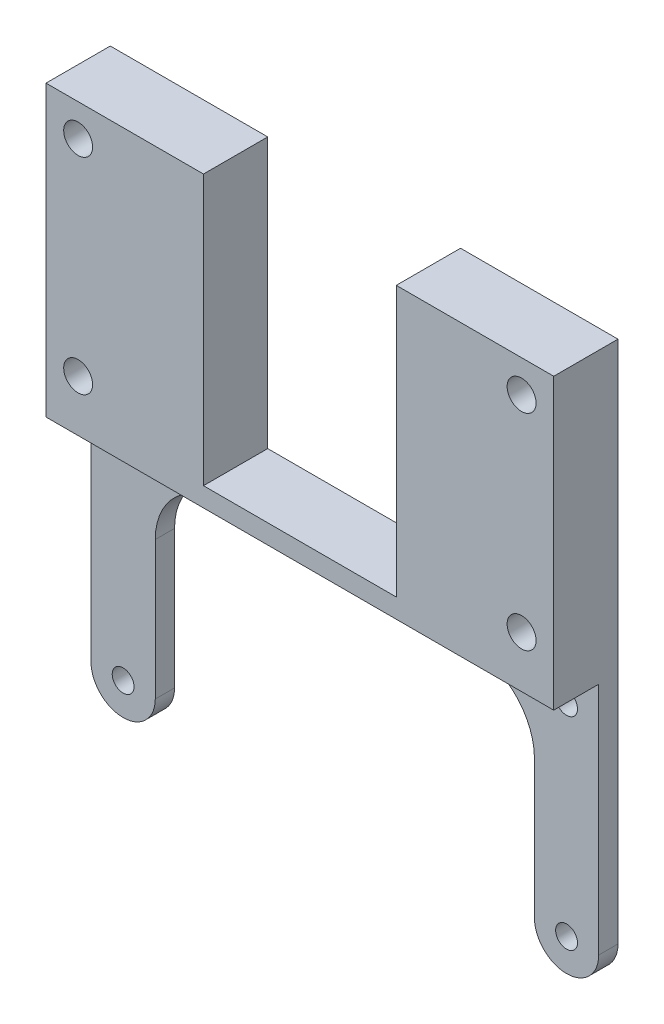
SolidWorks part; units mm, degrees
ref_plane "Front Plane" through (0, 0, 0) normal (0, 0, 1) x (1, 0, 0)
ref_plane "Top Plane" through (0, 0, 0) normal (0, 1, 0) x (1, 0, 0)
ref_plane "Right Plane" through (0, 0, 0) normal (1, 0, 0) x (0, 0, -1)
sketch "Sketch1" plane through (0, 0, 0) normal (0, 0, 1) x (1, 0, 0)
  line L0 (28.0246, -31.0442) -> (28.0246, 7.8468)
  line L1 (-40.9754, 12.8468) -> (38.0246, 12.8468)
  line L2 (-40.9754, 12.8468) -> (-40.9754, -28.6532)
  line L3 (-40.9754, -28.6532) -> (38.0246, -28.6532)
  line L4 (38.0246, 12.8468) -> (38.0246, -28.6532)
  line L5 (28.0246, -31.0442) -> (-30.9754, -31.0442)
  line L6 (28.0246, 7.8468) -> (-30.9754, 7.8468)
  line L7 (-30.9754, -31.0442) -> (-30.9754, 7.8468)
  line L8 (28.0246, -31.0442) -> (-30.9754, 7.8468) construction
  line L9 (28.0246, 7.8468) -> (-30.9754, -31.0442) construction
  point P5 (-1.4754, -11.5987)
  dimension "D1" = 79
  dimension "D2" = 41.5
  dimension "D3" = 5
  dimension "D4" = 10
  dimension "D5" = 10
extrude "Boss-Extrude1" add sketch "Sketch1" along normal blind 3 contours L3 L7 L6 L0 L4 L1 L2 region at (28.9169, -10.4032, 0)
fillet "Fillet1" radius 10 2 edges at (28.0246, 7.8468, 1.5) (-30.9754, 7.8468, 1.5)
fillet "Fillet2" radius 5 4 edges at (-30.9754, -28.6532, 1.5) (-40.9754, -28.6532, 1.5) (28.0246, -28.6532, 1.5) (38.0246, -28.6532, 1.5)
sketch "Sketch2" plane through (0, 0, 0) normal (0, 0, -1) x (-1, 0, 0)
  line L0 (40.9754, 12.8468) -> (40.9754, -23.6532) construction
  line L2 (40.9754, 12.8468) -> (-38.0246, 12.8468) construction
  line L3 (-38.0246, 12.8468) -> (-38.0246, -23.6532) construction
  point P0 (-33.0246, 7.8468)
  point P1 (35.9754, -23.6532)
  point P4 (-33.0246, -23.6532)
  point P11 (35.9754, 7.8468)
  dimension "D1" = 5
  dimension "D2" = 5
  dimension "D3" = 5
  dimension "D4" = 5
  dimension "D5" = 5
  dimension "D6" = 5
  dimension "D7" = 5
  dimension "D8" = 5
hole_wizard "M3 Clearance Hole1" positions "Sketch3" profile "Sketch4" hole size "M3" standard "ANSI Metric" end condition through all
sketch "Sketch3" plane through (0, 0, 0) normal (0, 0, -1) x (-1, 0, 0)
  point P0 (-33.0246, 7.8468)
  point P6 (35.9754, -23.6532)
  point P9 (35.9754, 7.8468)
  point P17 (-33.0246, -23.6532)
sketch "Sketch4" plane through (33.0246, 7.8468, 0) normal (1, 0, 0) x (0, 1, 0)
  line L0 (0, 0) -> (0, 3)
  line L1 (0, 3) -> (1.7, 3)
  line L2 (1.7, 3) -> (1.7, 0)
  line L5 (1.7, 0) -> (0, 0)
  line L11 (0, -6.35) -> (0, 107.95) construction
  dimension "Thru Hole Dia." = 3.4
  dimension "Thru Hole Depth" = 3
sketch "Sketch5" plane through (0, 0, 0) normal (0, 0, -1) x (-1, 0, 0)
  line L0 (40.9754, 12.8468) -> (40.9754, -23.6532) construction
  line L1 (-38.0246, 12.8468) -> (40.9754, 12.8468)
  line L2 (-38.0246, 12.8468) -> (-38.0246, 57.8468)
  line L3 (-38.0246, 57.8468) -> (40.9754, 57.8468)
  line L4 (40.9754, 12.8468) -> (40.9754, 57.8468)
  line L6 (16.4754, 15.8468) -> (-13.5246, 15.8468)
  line L7 (16.4754, 15.8468) -> (16.4754, 57.8468)
  line L8 (16.4754, 57.8468) -> (-13.5246, 57.8468)
  line L9 (-13.5246, 15.8468) -> (-13.5246, 57.8468)
  line L10 (16.4754, 15.8468) -> (-13.5246, 57.8468) construction
  line L11 (16.4754, 57.8468) -> (-13.5246, 15.8468) construction
  point P7 (1.4754, 36.8468)
  point P12 (1.4754, 57.8468)
  line M15 (40.9754, 12.8468) -> (-38.0246, 12.8468)
  dimension "D1" = 0
  dimension "D2" = 45
  dimension "D3" = 42
  dimension "D4" = 30
  dimension "D5" = 0
extrude "Boss-Extrude3" add sketch "Sketch5" along direction (0, 0, 1) on the side against the normal blind 10 contours L6 L9 L3 L2 L4 L7 M15 region at (37.1154, 35.3468, 0)
sketch "Sketch6" plane through (0, 0, 0) normal (0, 0, -1) x (-1, 0, 0)
  line L0 (16.4754, 57.8468) -> (40.9754, 57.8468) construction
  line L1 (16.4754, 15.8468) -> (-13.5246, 15.8468) construction
  point P0 (-33.0246, 20.8468)
  point P1 (35.9754, 52.8468)
  point P6 (-33.0246, 52.8468)
  point P7 (35.9754, 20.8468)
  dimension "D1" = 5
  dimension "D2" = 5
hole_wizard "M4 Clearance Hole1" positions "Sketch7" profile "Sketch8" hole size "M4" standard "ANSI Metric" end condition through all
sketch "Sketch7" plane through (0, 0, 0) normal (0, 0, -1) x (-1, 0, 0)
  point P0 (-33.0246, 52.8468)
  point P3 (-33.0246, 20.8468)
  point P6 (35.9754, 20.8468)
  point P9 (35.9754, 52.8468)
sketch "Sketch8" plane through (33.0246, 52.8468, 0) normal (1, 0, 0) x (0, 1, 0)
  line L0 (0, 0) -> (0, 10)
  line L1 (0, 10) -> (2.25, 10)
  line L2 (2.25, 10) -> (2.25, 0)
  line L5 (2.25, 0) -> (0, 0)
  line L11 (0, -6.35) -> (0, 107.95) construction
  dimension "Thru Hole Dia." = 4.5
  dimension "Thru Hole Depth" = 10
